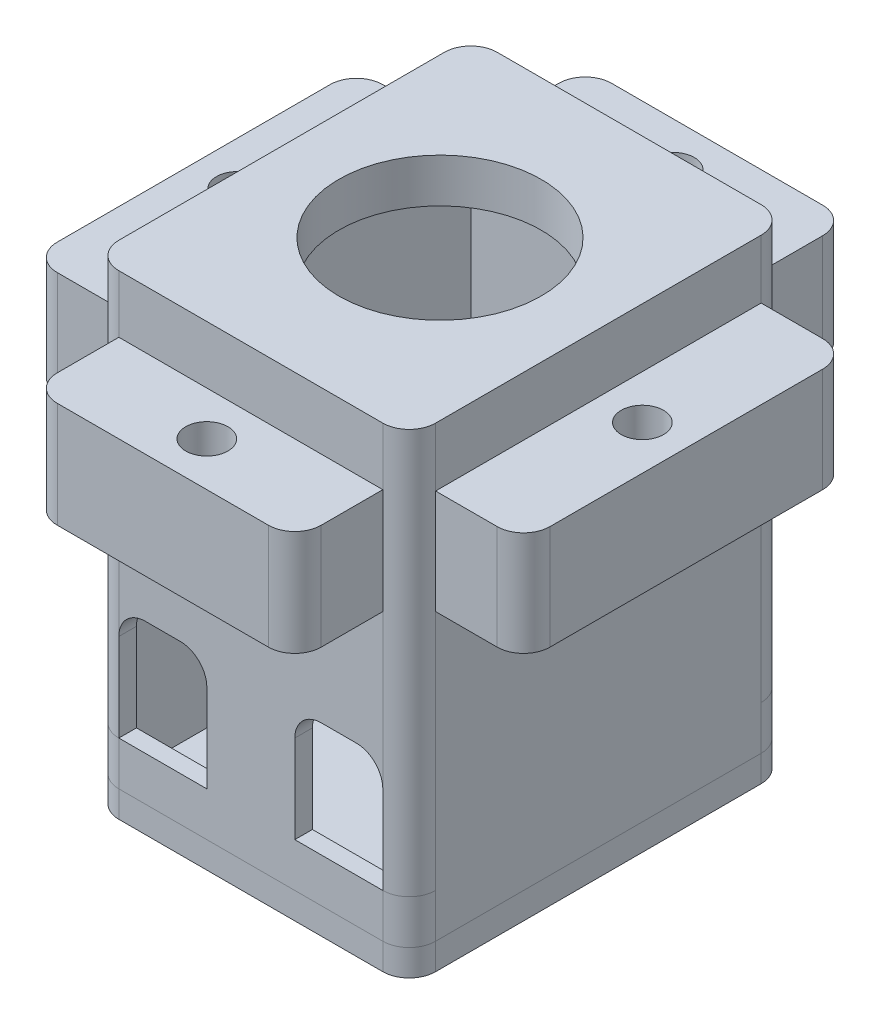
SolidWorks part; units mm, degrees
ref_plane "Front Plane" through (0, 0, 0) normal (0, 0, 1) x (1, 0, 0)
ref_plane "Top Plane" through (0, 0, 0) normal (0, 1, 0) x (1, 0, 0)
ref_plane "Right Plane" through (0, 0, 0) normal (1, 0, 0) x (0, 0, -1)
sketch "Sketch1" plane through (0, 0, 0) normal (0, 1, 0) x (1, 0, 0)
  line L1 (-16, -19.5) -> (16, -19.5)
  line L2 (-16, -19.5) -> (-16, 19.5)
  line L3 (-16, 19.5) -> (16, 19.5)
  line L4 (16, -19.5) -> (16, 19.5)
  line L5 (-16, -19.5) -> (16, 19.5) construction
  line L6 (-16, 19.5) -> (16, -19.5) construction
  line L7 (-18, -21.5) -> (18, -21.5)
  line L8 (-18, -21.5) -> (-18, 21.5)
  line L9 (-18, 21.5) -> (18, 21.5)
  line L10 (18, -21.5) -> (18, 21.5)
  line L11 (-18, -21.5) -> (18, 21.5) construction
  line L12 (-18, 21.5) -> (18, -21.5) construction
  point P0 (0, 0)
  point P6 (0, 0)
  dimension "D1" = 32
  dimension "D2" = 39
  dimension "D3" = 36
  dimension "D4" = 43
extrude "Boss-Extrude1" add sketch "Sketch1" along normal blind 46
sketch "Sketch2" plane through (0, 46, 0) normal (0, 1, 0) x (1, 0, 0)
  line L1 (-16, -19.5) -> (16, -19.5)
  line L2 (-16, -19.5) -> (-16, 19.5)
  line L3 (-16, 19.5) -> (16, 19.5)
  line L4 (16, -19.5) -> (16, 19.5)
  line L5 (-16, -19.5) -> (16, 19.5) construction
  line L6 (-16, 19.5) -> (16, -19.5) construction
  point P0 (0, 0)
extrude "Boss-Extrude2" add sketch "Sketch2" against normal blind 5
sketch "Sketch3" plane through (0, 46, 0) normal (0, 1, 0) x (1, 0, 0)
  circle A0 centre (0, 0) radius 11.5
  dimension "D1" = 23
extrude "Cut-Extrude1" cut sketch "Sketch3" against normal blind 5
sketch "Sketch4" plane through (0, 0, 21.5) normal (0, 0, 1) x (1, 0, 0)
  line L0 (-18, 0) -> (18, 0) construction
  line L1 (-15, 0) -> (-5, 0)
  line L2 (-15, 0) -> (-15, 13)
  line L3 (-15, 13) -> (-5, 13)
  line L4 (-5, 0) -> (-5, 13)
  line L5 (-18, 46) -> (-18, 0) construction
  line L6 (15, 0) -> (5, 0)
  line L7 (15, 0) -> (15, 13)
  line L8 (15, 13) -> (5, 13)
  line L9 (5, 0) -> (5, 13)
  line L10 (18, 46) -> (18, 0) construction
  dimension "D1" = 3
  dimension "D2" = 3
  dimension "D3" = 13
  dimension "D4" = 13
  dimension "D5" = 10
  dimension "D6" = 10
extrude "Cut-Extrude2" cut sketch "Sketch4" against normal through all contours L2 L1 L4 L3 | L7 L6 L9 L8
sketch "Sketch5" plane through (-18, 0, 0) normal (-1, 0, 0) x (0, 0, 1)
  line L0 (21.5, 46) -> (21.5, 0) construction
  line L1 (-21.5, 46) -> (21.5, 46)
  line L2 (-21.5, 46) -> (-21.5, 41)
  line L3 (-21.5, 41) -> (21.5, 41)
  line L4 (21.5, 46) -> (21.5, 41)
  line L5 (-21.5, 46) -> (-21.5, 0) construction
  line L6 (-21.5, 15) -> (21.5, 15)
  line L7 (-21.5, 15) -> (-21.5, 20)
  line L8 (-21.5, 20) -> (21.5, 20)
  line L9 (21.5, 15) -> (21.5, 20)
  line L10 (-21.5, 0) -> (21.5, 0) construction
  dimension "D1" = 5
  dimension "D2" = 5
  dimension "D3" = 15
extrude "Boss-Extrude3" [suppressed] add sketch "Sketch5" along normal blind 10
sketch "Sketch8" [suppressed] plane through (0, 46, 0) normal (0, 1, 0) x (1, 0, 0)
  line L0 (18, 21.5) -> (-28, 21.5) construction
  line L1 (-28, -21.5) -> (18, -21.5) construction
  line L2 (-28, -21.5) -> (-28, 21.5) construction
  circle A0 centre (-23, 16.5) radius 2
  circle A1 centre (-23, -16.5) radius 2
  dimension "D1" = 5
  dimension "D2" = 5
  dimension "D3" = 5
  dimension "D5" = 4
  dimension "D6" = 4
  dimension "D4" = 5
extrude "Cut-Extrude4" [suppressed] cut sketch "Sketch8" against normal blind 34
fillet "Fillet3" radius 3 8 edges at (-15, 13, -20.5) (-5, 13, -20.5) (5, 13, -20.5) (15, 13, -20.5) (15, 13, 20.5) (5, 13, 20.5) (-5, 13, 20.5) (-15, 13, 20.5)
fillet "Fillet4" radius 3 2 edges at (-18, 23, 21.5) (-18, 23, -21.5)
fillet "Fillet5" radius 3 2 edges at (18, 23, -21.5) (18, 23, 21.5)
sketch "Sketch10" plane through (0, 0, 0) normal (0, -1, 0) x (1, 0, 0)
  line L4 (18, 21.5) -> (-18, 21.5)
  line L5 (18, -21.5) -> (18, 21.5)
  line L6 (-18, -21.5) -> (18, -21.5)
  line L7 (-18, 21.5) -> (-18, -21.5)
  line L8 (18, 21.5) -> (-18, 21.5)
  line L9 (18, -21.5) -> (18, 21.5)
  line L10 (-18, -21.5) -> (18, -21.5)
  line L11 (-18, 21.5) -> (-18, -21.5)
  dimension "D1" = 0
extrude "Boss-Extrude6" add sketch "Sketch10" along normal blind 3 from offset 5
fillet "Fillet6" radius 3 rebuild error yes
sketch "Sketch11" plane through (0, 0, 0) normal (0, -1, 0) x (1, 0, 0)
  line L4 (18, 21.5) -> (-18, 21.5)
  line L5 (18, -21.5) -> (18, 21.5)
  line L6 (-18, -21.5) -> (18, -21.5)
  line L7 (-18, 21.5) -> (-18, -21.5)
  line L8 (18, 21.5) -> (-18, 21.5)
  line L9 (18, -21.5) -> (18, 21.5)
  line L10 (-18, -21.5) -> (18, -21.5)
  line L11 (-18, 21.5) -> (-18, -21.5)
  line L24 (16, 19.5) -> (-16, 19.5)
  line L25 (16, -19.5) -> (16, 19.5)
  line L26 (-16, -19.5) -> (16, -19.5)
  line L27 (-16, 19.5) -> (-16, -19.5)
  line L28 (16, 19.5) -> (-16, 19.5)
  line L29 (16, -19.5) -> (16, 19.5)
  line L30 (-16, -19.5) -> (16, -19.5)
  line L31 (-16, 19.5) -> (-16, -19.5)
  dimension "D1" = 0
  dimension "D3" = 0
extrude "Boss-Extrude7" add sketch "Sketch11" along normal blind 5
fillet "Fillet7" radius 3 4 edges at (-18, -2.5, -21.5) (18, -2.5, -21.5) (18, -2.5, 21.5) (-18, -2.5, 21.5)
fillet "Fillet8" radius 3 4 edges at (18, -6.5, 21.5) (-18, -6.5, 21.5) (-18, -6.5, -21.5) (18, -6.5, -21.5)
sketch "Sketch12" plane through (-18, 0, 0) normal (-1, 0, 0) x (0, 0, 1)
  line L0 (-3, 19) -> (3, 19)
  line L2 (18.5, -8) -> (-18.5, -8) construction
  line L4 (3, 19) -> (3, -8)
  line L5 (-3, 19) -> (-3, -8)
  line L6 (3, -8) -> (-3, -8)
extrude "Boss-Extrude8" add sketch "Sketch12" along normal blind 15 separate body
sketch "Sketch13" plane through (0, 0, -3) normal (0, 0, -1) x (-1, 0, 0)
  line L0 (18, 46) -> (33, -5)
  line L1 (33, -5) -> (33, 46)
  line L2 (33, 46) -> (18, 46)
extrude "Cut-Extrude5" cut sketch "Sketch13" against normal blind 15
sketch "Sketch14" plane through (0, -5, 0) normal (0, -1, 0) x (1, 0, 0)
  line L1 (-33, 3) -> (-18, 3)
  line L2 (-33, 3) -> (-33, -3)
  line L3 (-33, -3) -> (-18, -3)
  line L4 (-18, 3) -> (-18, -3)
extrude "Boss-Extrude9" add sketch "Sketch14" along normal blind 3
sketch "Sketch15" plane through (0, 0, -21.5) normal (0, 0, -1) x (-1, 0, 0)
  line L0 (-15, 46) -> (-15, 10) construction
  line L1 (-15, 39.4486) -> (15, 39.4486)
  line L2 (-15, 39.4486) -> (-15, 27.4486)
  line L3 (-15, 27.4486) -> (15, 27.4486)
  line L4 (15, 39.4486) -> (15, 27.4486)
  line L5 (15, 10) -> (15, 46) construction
  dimension "D1" = 12
extrude "Boss-Extrude10" add sketch "Sketch15" along normal blind 10
mirror "Mirror4" about plane through (0, 0, 0) normal (0, 0, 1) of "Boss-Extrude10"
sketch "Sketch16" plane through (18, 0, 0) normal (1, 0, 0) x (0, 0, -1)
  line L0 (-18.5, 46) -> (-18.5, 0) construction
  line L1 (-18.5, 39.3164) -> (18.5, 39.3164)
  line L2 (-18.5, 39.3164) -> (-18.5, 27.4486)
  line L3 (-18.5, 27.4486) -> (18.5, 27.4486)
  line L4 (18.5, 39.3164) -> (18.5, 27.4486)
  line L5 (18.5, 0) -> (18.5, 46) construction
extrude "Boss-Extrude11" add sketch "Sketch16" along normal blind 10
mirror "Mirror5" about plane through (0, 0, 0) normal (1, 0, 0) of "Boss-Extrude11"
fillet "Fillet9" radius 3 8 edges at (-28, 33.3825, -18.5) (-28, 33.3825, 18.5) (-15, 33.4486, 31.5) (15, 33.4486, 31.5) (28, 33.3825, 18.5) (28, 33.3825, -18.5) (15, 33.4486, -31.5) (-15, 33.4486, -31.5)
sketch "Sketch17" plane through (0, 39.4486, 0) normal (0, 1, 0) x (1, 0, 0)
  line L0 (-15, 28.5) -> (-15, 21.5) construction
  line L4 (-12, 31.5) -> (12, 31.5) construction
  circle A2 centre (0, 26.5) radius 2.4
  dimension "D2" = 15
  dimension "D3" = 5
  dimension "D1" = 4.8
extrude "Cut-Extrude6" cut sketch "Sketch17" against normal blind 17
mirror "Mirror6" about plane through (0, 0, 0) normal (0, 0, 1) of "Cut-Extrude6"
sketch "Sketch18" plane through (0, 39.3164, 0) normal (0, 1, 0) x (1, 0, 0)
  line L0 (-28, 15.5) -> (-28, -15.5) construction
  circle A0 centre (-23, 0) radius 2.4
  dimension "D1" = 4.8
  dimension "D2" = 5
extrude "Cut-Extrude7" cut sketch "Sketch18" against normal blind 17
mirror "Mirror7" about plane through (0, 0, 0) normal (1, 0, 0) of "Cut-Extrude7"
